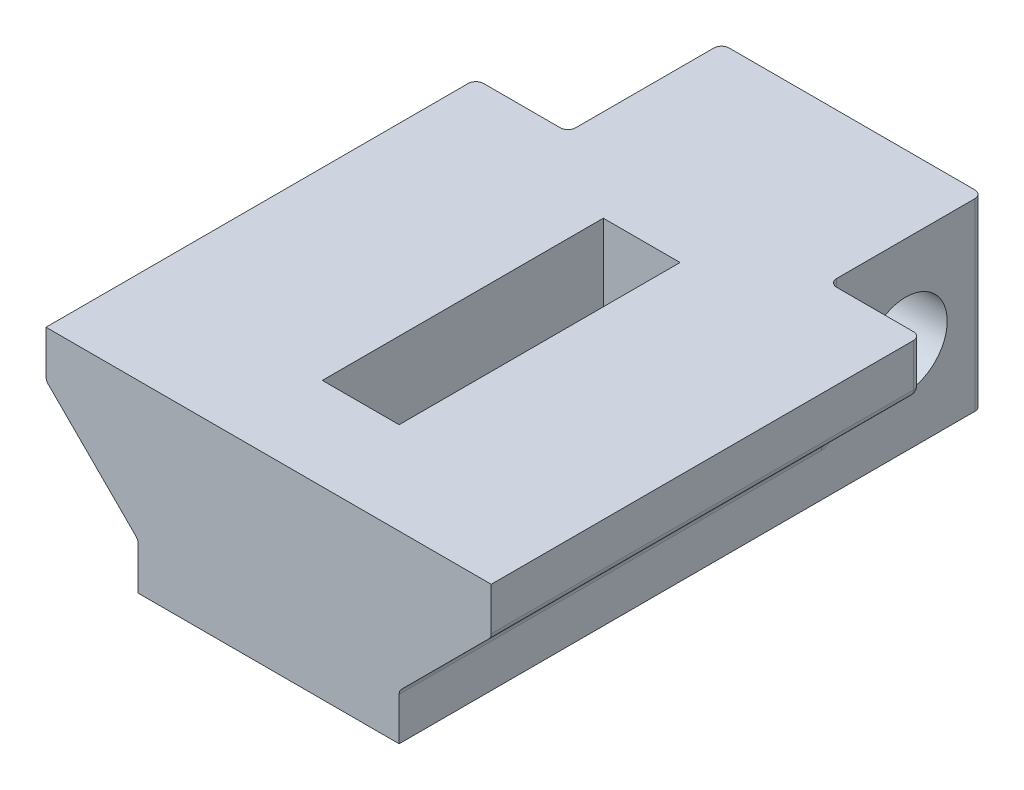
SolidWorks part; units mm, degrees
material "ABS"
ref_plane "Front Plane" through (0, 0, 0) normal (0, 0, 1) x (1, 0, 0)
ref_plane "Top Plane" through (0, 0, 0) normal (0, 1, 0) x (1, 0, 0)
ref_plane "Right Plane" through (0, 0, 0) normal (1, 0, 0) x (0, 0, -1)
sketch "Sketch1" plane through (0, 0, 0) normal (0, 0, 1) x (1, 0, 0)
  line L0 (0, 0) -> (0, 12) construction
  line L1 (-14.5, 12) -> (-14.5, 9)
  line L2 (-14.5, 9) -> (-8.5, 3)
  line L3 (-8.5, 3) -> (-8.5, 0)
  line L4 (8.5, 3) -> (8.5, 0)
  line L5 (14.5, 9) -> (8.5, 3)
  line L6 (14.5, 12) -> (14.5, 9)
  line L7 (-14.5, 12) -> (14.5, 12)
  line L8 (-8.5, 0) -> (8.5, 0)
  dimension "D1" = 12
  dimension "D2" = 3
  dimension "D3" = 45
  dimension "D4" = 17
extrude "Dovetail Body" add sketch "Sketch1" along normal mid plane 38
sketch "Sketch9" plane through (0, 0, -19) normal (0, 0, -1) x (-1, 0, 0)
  line L0 (0, 12) -> (0, 0) construction
  line L1 (-14.5, 12) -> (-8.5, 12)
  line L2 (-14.5, 12) -> (-14.5, 0)
  line L3 (-14.5, 0) -> (-8.5, 0)
  line L4 (-8.5, 12) -> (-8.5, 0)
  line L5 (-14.5, 12) -> (14.5, 12) construction
  line L6 (8.5, 0) -> (-8.5, 0) construction
  line L7 (8.5, 12) -> (8.5, 0)
  line L8 (14.5, 0) -> (8.5, 0)
  line L9 (14.5, 12) -> (14.5, 0)
  line L10 (14.5, 12) -> (8.5, 12)
extrude "Bolt Clearance" cut sketch "Sketch9" against normal blind 10
sketch "Sketch10" plane through (8.5, 0, 0) normal (1, 0, 0) x (0, 0, -1)
  line L0 (14, 12) -> (14, 0) construction
  line L1 (9, 12) -> (19, 12) construction
  line L2 (-19, 0) -> (19, 0) construction
  circle A0 centre (14, 6) radius 2.7
  dimension "D1" = 5.4
extrude "Bolt Insert" cut sketch "Sketch10" against normal through all
sketch "Sketch11" plane through (0, 0, 0) normal (0, -1, 0) x (1, 0, 0)
  line L0 (0, -5.3) -> (0, 0) construction
  line L1 (2.5, -5.3) -> (-2.5, -5.3)
  line L2 (2.5, -5.3) -> (2.5, 13)
  line L3 (2.5, 13) -> (-2.5, 13)
  line L4 (-2.5, -5.3) -> (-2.5, 13)
  line L5 (8.5, 19) -> (8.5, -19) construction
  line L6 (-8.5, 19) -> (8.5, 19) construction
  line L7 (8.5, -16.7) -> (8.5, -11.3) construction
  line L8 (8.5, -16.7) -> (8.5, -11.3) construction
  dimension "D1" = 6
  dimension "D2" = 6
  dimension "D3" = 6
extrude "Weight Clearance" cut sketch "Sketch11" against normal through all
fillet "Contouring" radius 0.5 12 edges at (8.5, 7.5, -9) (-8.5, 7.5, -9) (8.5, 3, 5) (-8.5, 3, 5) (-14.5, 9, 5) (14.5, 9, 5) (-11.5, 6, -9) (-14.5, 10.5, -9) (-8.5, 6, -19) (8.5, 6, -19) (11.5, 6, -9) (14.5, 10.5, -9)
equation "\"width keep\" = 3"
equation "\"dovetail height\"= 12"
equation "\"dovetail angle\"= 45"
equation "\"dovetail width\"= 17"
equation "\"D1@Sketch1\"=\"dovetail height\""
equation "\"D2@Sketch1\"=\"width keep\""
equation "\"D3@Sketch1\"=\"dovetail angle\""
equation "\"D4@Sketch1\"=\"dovetail width\""
equation "\"dovetail length\"= 38"
equation "\"D1@Dovetail Body\" = \"dovetail length\""
equation "\"print free\"= 0.45"
equation "\"print fit\"= 0.2"
equation "\"D1@Sketch11\"=2*\"width keep\""
equation "\"D2@Sketch11\"=\"D1@Sketch11\""
equation "\"D3@Sketch11\"=\"D2@Sketch11\""
